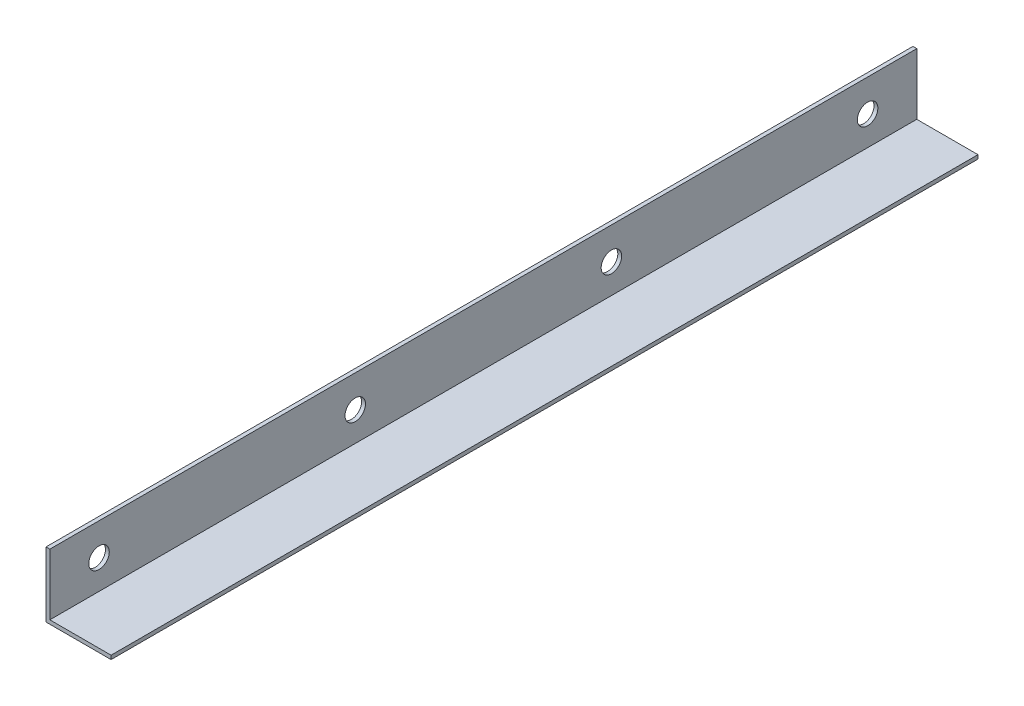
SolidWorks part; units mm, degrees
material "AISI 1015 Acero estirado en frío (SS)"
ref_plane "Alzado" through (0, 0, 0) normal (0, 0, 1) x (1, 0, 0)
ref_plane "Planta" through (0, 0, 0) normal (0, 1, 0) x (1, 0, 0)
ref_plane "Vista lateral" through (0, 0, 0) normal (1, 0, 0) x (0, 0, -1)
sketch "Croquis1" plane through (0, 0, 0) normal (0, 0, 1) x (1, 0, 0)
  line L0 (0, 0) -> (0, 25.4)
  line L1 (0, 0) -> (25.4, 0)
  line L2 (1.5, 1.5) -> (25.4, 1.5)
  line L3 (1.5, 1.5) -> (1.5, 25.4)
  line L4 (0, 25.4) -> (1.5, 25.4)
  line L5 (25.4, 1.5) -> (25.4, 0)
  dimension "D1" = 25.4
  dimension "D2" = 1.5
extrude "Saliente-Extruir1" add sketch "Croquis1" along normal blind 338.4
sketch "Croquis2" plane through (1.5, 0, 0) normal (1, 0, 0) x (0, 0, -1)
  line L0 (-169.2, 25.4) -> (-169.2, -16.8319) construction
  line L1 (-338.4, 25.4) -> (0, 25.4) construction
  line L2 (-338.4, 12.9) -> (0, 12.9) construction
  line L3 (-338.4, 1.5) -> (-338.4, 25.4) construction
  line L4 (0, 1.5) -> (0, 25.4) construction
  line L5 (-338.4, 1.5) -> (0, 1.5) construction
  circle A0 centre (-219.2, 12.9) radius 4
  circle A1 centre (-119.2, 12.9) radius 4
  circle A2 centre (-19.2, 12.9) radius 4
  circle A3 centre (-319.2, 12.9) radius 4
  dimension "D6" = 8
  dimension "D1" = 11.4
  dimension "D2" = 50
  dimension "D3" = 50
  dimension "D4" = 100
  dimension "D5" = 100
extrude "Cortar-Extruir1" cut sketch "Croquis2" against normal blind 2
